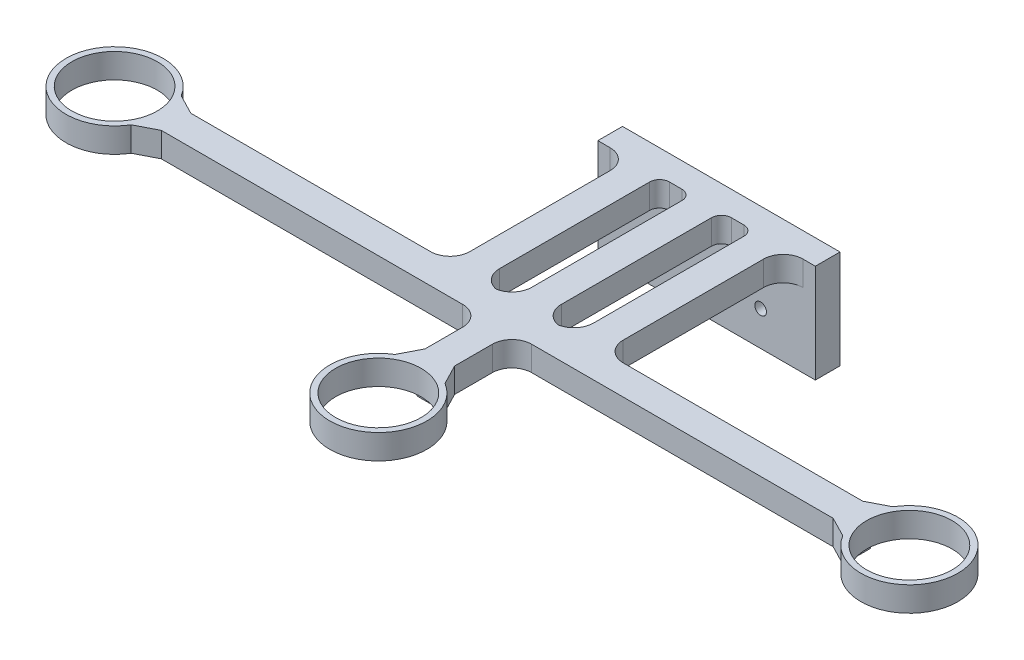
SolidWorks part; units mm, degrees
ref_plane "Front Plane" through (0, 0, 0) normal (0, 0, 1) x (1, 0, 0)
ref_plane "Top Plane" through (0, 0, 0) normal (0, 1, 0) x (1, 0, 0)
ref_plane "Right Plane" through (0, 0, 0) normal (1, 0, 0) x (0, 0, -1)
sketch "Sketch1" plane through (0, 0, 0) normal (0, 0, 1) x (1, 0, 0)
  line L0 (0, 0) -> (55.9994, 0)
  line L1 (55.9994, 0) -> (55.9994, -25.4)
  line L2 (55.9994, -25.4) -> (0, -25.4)
  line L3 (0, -25.4) -> (0, 0)
  dimension "D1" = 55.9994
  dimension "D2" = 25.4
extrude "Boss-Extrude1" add sketch "Sketch1" along normal blind 6.35
sketch "Sketch2" plane through (0, 0, 0) normal (0, 1, 0) x (1, 0, 0)
  line L0 (118.4205, -52.6461) -> (62.9313, -52.6461)
  line L1 (55.9994, -6.35) -> (0, -6.35) construction
  line L2 (256.7309, -56.4561) -> (62.9314, -56.4561) construction
  line L3 (-6.9816, -52.6461) -> (8.2625, -52.6461)
  line L4 (27.9997, -6.35) -> (31.8097, -6.35)
  line L5 (27.9997, -6.35) -> (24.1897, -6.35)
  line L6 (24.1897, -6.35) -> (24.1897, -52.6461)
  line L7 (31.8097, -6.35) -> (31.8097, -52.6461)
  line L8 (43.9344, -37.4591) -> (43.9344, -33.7021) construction
  line L9 (43.9344, -6.35) -> (47.7444, -6.35)
  line L10 (43.9344, -6.35) -> (43.9344, -33.7021) construction
  line L11 (43.9344, -6.35) -> (40.1243, -6.35)
  line L12 (12.065, -6.35) -> (8.2625, -6.35)
  line L13 (12.065, -6.35) -> (12.065, -33.7021) construction
  line L14 (12.065, -6.35) -> (15.8825, -6.35)
  line L15 (118.4205, -60.2661) -> (62.9313, -60.2661)
  line L16 (27.9997, -6.35) -> (27.9997, -78.3691) construction
  line L17 (-6.9816, -60.2661) -> (24.1897, -60.2661)
  line L18 (40.1243, -37.459) -> (40.1243, -6.35)
  line L19 (-6.9816, -60.2661) -> (-62.4211, -60.2661)
  line L20 (47.7444, -29.8921) -> (47.7444, -6.35)
  line L21 (12.065, -33.7021) -> (12.065, -37.4057) construction
  line L22 (8.2625, -37.4019) -> (8.2625, -52.6461)
  line L23 (47.7444, -37.459) -> (47.7444, -52.6461)
  line L24 (15.8825, -37.4019) -> (15.8825, -52.6461)
  line L25 (8.2625, -29.8849) -> (8.2625, -6.35)
  line L26 (40.1243, -37.459) -> (40.1243, -52.6461)
  line L27 (15.8825, -37.4019) -> (15.8825, -6.35)
  line L28 (-62.4211, -52.6461) -> (-6.9816, -52.6461)
  line L29 (47.7444, -37.459) -> (47.7444, -29.8921)
  line L30 (8.2625, -37.4019) -> (8.2625, -29.8849)
  line L31 (24.1897, -60.2661) -> (24.1897, -78.9639)
  line L32 (31.8097, -60.2661) -> (31.8097, -78.9639)
  line L33 (15.8825, -52.6461) -> (24.1897, -52.6461)
  line L34 (-200.7315, -56.4561) -> (-6.9854, -56.4561) construction
  line L35 (31.8097, -52.6461) -> (40.1243, -52.6461)
  line L36 (47.7444, -52.6461) -> (62.9313, -52.6461)
  line L37 (31.8097, -60.2661) -> (62.9313, -60.2661)
  circle A0 centre (27.9997, -6.35) radius 84.5191 construction
  circle A1 centre (27.9997, -90.8691) radius 12.5
  circle A2 centre (130.3257, -56.4561) radius 12.5
  arc A3 (40.1243, -37.459) -> (62.9313, -60.2661) centre (62.9313, -37.459) ccw construction
  circle A4 centre (27.9997, -6.35) radius 246.38 construction
  circle A5 centre (-74.3263, -56.4561) radius 12.5
  arc A6 (47.7444, -37.459) -> (62.9313, -52.6461) centre (62.9314, -37.4591) ccw construction
  arc A7 (15.8825, -37.4019) -> (-6.9816, -60.2661) centre (-6.9816, -37.4019) cw construction
  arc A8 (8.2625, -37.4019) -> (-6.9816, -52.6461) centre (-6.9816, -37.4019) cw construction
  arc A9 (-6.9854, -56.4561) -> (12.065, -37.4057) centre (-6.9854, -37.4057) ccw construction
  arc A10 (43.9344, -37.4591) -> (62.9314, -56.4561) centre (62.9314, -37.4591) ccw construction
  dimension "D1" = 25
  dimension "D2" = 25
  dimension "D4" = 25
sketch "Sketch9" plane through (0, 0, 6.35) normal (0, 0, 1) x (1, 0, 0)
  circle A0 centre (13.97, -16.51) radius 1.5
  circle A1 centre (41.91, -16.51) radius 1.5
  dimension "D1" = 3
  dimension "D2" = 3
extrude "Boss-Extrude2" add sketch "Sketch2" against normal blind 6.35
sketch "Sketch10" plane through (0, 0, 0) normal (0, 1, 0) x (1, 0, 0)
  circle A0 centre (-74.3263, -56.4561) radius 11
  circle A1 centre (27.9997, -90.8691) radius 11
  circle A2 centre (130.3257, -56.4561) radius 11
  dimension "D1" = 22
  dimension "D2" = 22
  dimension "D3" = 22
extrude "Cut-Extrude3" cut sketch "Sketch10" against normal through all
fillet "Fillet1" radius 5.08 1 edges at (8.2625, -3.175, 6.35)
fillet "Fillet2" radius 5.08 1 edges at (47.7444, -3.175, 6.35)
fillet "Fillet3" radius 5.08 1 edges at (47.7444, -3.175, 52.6461)
fillet "Fillet4" radius 5.08 1 edges at (8.2625, -3.175, 52.6461)
fillet "Fillet5" radius 5.08 2 edges at (24.1897, -3.175, 60.2661) (31.8097, -3.175, 60.2661)
fillet "Fillet6" radius 5.08 4 edges at (40.1243, -3.175, 52.6461) (24.1897, -3.175, 52.6461) (31.8097, -3.175, 52.6461) (15.8825, -3.175, 52.6461)
fillet "Fillet7" radius 2.54 4 edges at (15.8825, -3.175, 6.35) (24.1897, -3.175, 6.35) (31.8097, -3.175, 6.35) (40.1243, -3.175, 6.35)
extrude "Cut-Extrude2" cut sketch "Sketch9" against normal through all
sketch "Sketch13" plane through (0, -6.35, 0) normal (0, -1, 0) x (1, 0, 0)
  line L0 (-62.4211, 56.4561) -> (-7.016, 56.4561) construction
  line L1 (12.0725, 6.35) -> (12.0039, 37.478) construction
  line L2 (-62.4211, 56.4561) -> (-62.4211, 54.5511)
  line L3 (8.2625, 6.35) -> (15.8825, 6.35) construction
  line L4 (27.9997, 6.35) -> (27.9997, 79.8691) construction
  line L5 (24.1897, 6.35) -> (31.8097, 6.35) construction
  line L6 (43.9343, 6.35) -> (43.9343, 37.459) construction
  line L8 (118.4205, 56.4561) -> (62.9314, 56.4561) construction
  line L9 (-62.4211, 56.4561) -> (-62.4211, 58.3611)
  line L10 (-62.4211, 58.3611) -> (-6.9892, 58.3611)
  line L11 (42.0294, 6.35) -> (42.0294, 37.4591)
  line L12 (-62.4211, 54.5511) -> (-6.9854, 54.5511)
  line L13 (-6.9892, 58.3611) -> (62.9314, 58.3611)
  line L14 (12.0725, 6.35) -> (13.97, 6.35)
  line L15 (0, 6.35) -> (55.9994, 6.35) construction
  line L16 (12.0725, 6.35) -> (10.16, 6.35)
  line L17 (10.16, 6.35) -> (10.16, 37.4057)
  line L18 (13.97, 6.35) -> (13.9468, 37.4407)
  line L19 (42.0294, 6.35) -> (45.8394, 6.35)
  line L21 (257.3257, 56.4561) -> (257.3257, 58.3611)
  line L22 (257.3257, 56.4561) -> (257.3257, 54.5511)
  line L23 (118.4205, 56.4561) -> (118.4205, 58.3611)
  line L24 (45.8394, 6.35) -> (45.8394, 37.4591)
  line L25 (118.4205, 56.4561) -> (118.4205, 54.5511)
  line L26 (26.0947, 78.9639) -> (29.9047, 78.9639)
  line L27 (27.9997, 6.35) -> (29.9047, 6.35)
  line L28 (27.9997, 6.35) -> (26.0947, 6.35)
  line L29 (26.0947, 6.35) -> (26.0947, 78.9639)
  line L30 (29.9047, 6.35) -> (29.9047, 78.9639)
  line L31 (118.4205, 58.3611) -> (62.9314, 58.3611)
  line L32 (118.4205, 54.5511) -> (62.9314, 54.5511)
  line L33 (-6.9854, 54.5511) -> (62.9314, 54.5511)
  line L34 (10.16, 37.4057) -> (10.16, 54.5511)
  line L35 (13.9468, 37.4407) -> (13.9468, 54.5511)
  line L36 (42.0294, 37.4591) -> (42.0294, 54.5511)
  line L37 (45.8394, 37.4591) -> (45.8394, 54.5511)
  circle A1 centre (27.9997, 90.8691) radius 11 construction
  line M74 (3.1825, 6.35) -> (18.4225, 6.35)
  line M87 (37.5843, 6.35) -> (52.8244, 6.35)
extrude "Boss-Extrude3" add sketch "Sketch13" along normal blind 1.27 contours L12 L33 L29 L13 L10 L9 L2 | L30 L33 L32 L25 L23 L31 L13 | L29 L33 L30 L13 | L18 L35 L33 L34 L17 M74 | L24 L37 L33 L36 L11 M87
fillet "Fillet8" radius 1.27 6 edges at (45.8394, -6.985, 6.35) (29.9047, -6.985, 6.35) (42.0294, -6.985, 6.35) (26.0947, -6.985, 6.35) (13.97, -6.985, 6.35) (10.16, -6.985, 6.35)
chamfer "Chamfer1" distance 2.54 angle 45 2 edges at (-62.4211, -3.175, 60.2661) (-62.4211, -3.175, 52.6461)
chamfer "Chamfer3" distance 2.54 angle 45 2 edges at (118.4205, -3.175, 52.6461) (118.4205, -3.175, 60.2661)
chamfer "Chamfer4" distance 2.54 angle 45 2 edges at (31.8097, -3.175, 78.9639) (24.1897, -3.175, 78.9639)
